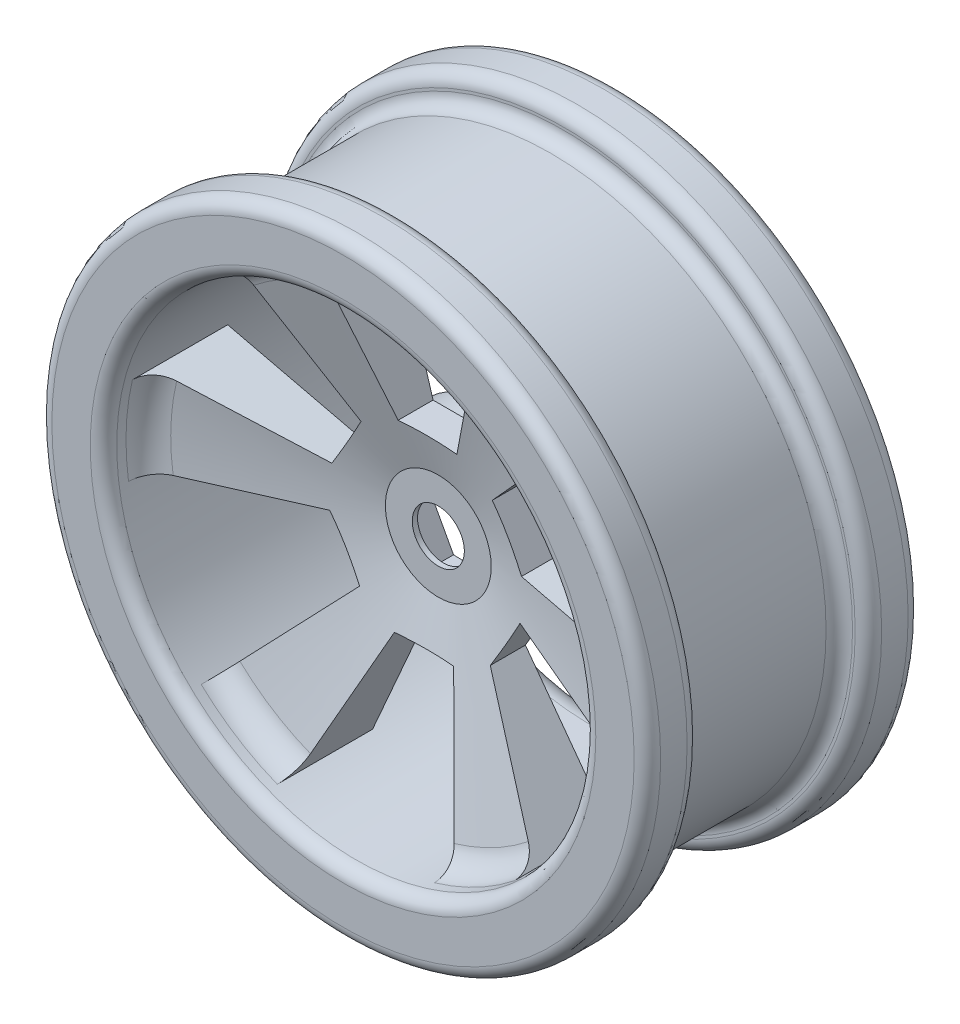
SolidWorks part; units mm, degrees
material "ABS"
ref_plane "Front Plane" through (0, 0, 0) normal (0, 0, 1) x (1, 0, 0)
ref_plane "Top Plane" through (0, 0, 0) normal (0, 1, 0) x (1, 0, 0)
ref_plane "Right Plane" through (0, 0, 0) normal (1, 0, 0) x (0, 0, -1)
sketch "Sketch1" plane through (0, 0, 0) normal (1, 0, 0) x (0, 0, -1)
  line L0 (0, 0) -> (59.5506, 0) construction
  line L1 (0, 0) -> (0, 22.987) construction
  line L2 (0, 22.987) -> (15.24, 22.987) construction
  line L3 (17.78, 25.527) -> (17.78, 27.94)
  line L4 (16.51, 29.21) -> (13.97, 29.21)
  line L5 (12.7, 27.94) -> (12.7, 27.686)
  line L6 (11.43, 26.416) -> (-2.159, 26.416)
  line L7 (-3.429, 27.686) -> (-3.429, 27.94)
  line L8 (-4.699, 29.21) -> (-7.239, 29.21)
  line L9 (-8.509, 27.94) -> (-8.509, 24.257)
  line L10 (-7.239, 22.987) -> (-6.35, 22.987)
  line L11 (0.635, 0) -> (0.635, 5.08)
  line L12 (-3.81, 0) -> (0, 0)
  line L13 (2.794, 22.987) -> (15.24, 22.987)
  line L14 (2.794, 22.987) -> (2.794, 8.4709)
  line L15 (2.794, 8.4709) -> (5.715, 8.4709)
  line L16 (5.715, 8.4709) -> (5.715, 0)
  line L17 (5.715, 0) -> (0, 0)
  line L18 (-3.9058, 21.1381) -> (0.635, 5.08)
  line L19 (5.715, 0) -> (1.143, 0) construction
  line L20 (5.715, 0) -> (5.715, 7.3033) construction
  line L21 (5.715, 7.3033) -> (1.143, 7.3033) construction
  line L22 (1.143, 0) -> (1.143, 7.3033) construction
  line L23 (5.715, 0) -> (1.143, 7.3033) construction
  line L24 (5.715, 7.3033) -> (1.143, 0) construction
  arc A0 (-6.35, 22.987) -> (-3.9058, 21.1381) centre (-6.35, 20.447) cw
  arc A1 (16.51, 29.21) -> (17.78, 27.94) centre (16.51, 27.94) cw
  arc A2 (13.97, 29.21) -> (12.7, 27.94) centre (13.97, 27.94) ccw
  arc A3 (-7.239, 29.21) -> (-8.509, 27.94) centre (-7.239, 27.94) ccw
  arc A4 (-4.699, 29.21) -> (-3.429, 27.94) centre (-4.699, 27.94) cw
  arc A5 (12.7, 27.686) -> (11.43, 26.416) centre (11.43, 27.686) cw
  arc A6 (-3.429, 27.686) -> (-2.159, 26.416) centre (-2.159, 27.686) ccw
  arc A7 (-7.239, 22.987) -> (-8.509, 24.257) centre (-7.239, 24.257) cw
  arc A8 (17.78, 25.527) -> (15.24, 22.987) centre (15.24, 25.527) cw
  point P22 (12.7, 29.21)
  point P29 (12.7, 26.416)
  point P36 (17.78, 22.987)
  point P42 (3.429, 3.6516)
  dimension "D8" = 2.54
  dimension "D9" = 1.27
  dimension "D10" = 2.54
  dimension "D11" = 45.974
  dimension "D1" = 58.42
  dimension "D2" = 2.794
  dimension "D3" = 14.986
  dimension "D4" = 5.08
  dimension "D5" = 10.16
  dimension "D6" = 26.289
  dimension "D7" = 17.78
  dimension "D12" = 16.9418
  dimension "D13" = 12.065
  dimension "D14" = 4.572
  dimension "D15" = 0.508
revolve "Body" add sketch "Sketch1" angle 360 about L0 region at (0, 24.0088, -16.7582)
sketch "Sketch2" plane through (0, 0, 0) normal (0, 0, 1) x (1, 0, 0)
  line L0 (-2.6636, 8.89) -> (2.9969, 8.89)
  line L1 (3.3042, -6.0895) -> (6.9258, -0.1832)
  line L2 (6.9258, -0.1832) -> (3.6216, 5.9063)
  line L3 (3.6216, 5.9063) -> (-3.3042, 6.0895)
  line L4 (-3.3042, 6.0895) -> (-6.9258, 0.1832)
  line L5 (-6.9258, 0.1832) -> (-3.6216, -5.9063)
  line L6 (-3.6216, -5.9063) -> (3.3042, -6.0895)
  line L7 (2.9969, 8.89) -> (8.47, 21.3696)
  line L8 (-2.6636, 8.89) -> (-6.5976, 22.0199)
  circle A0 centre (0, 0) radius 6 construction
  arc A2 (-6.5976, 22.0199) -> (8.47, 21.3696) centre (0, 0) cw
  circle A3 centre (0, 0) radius 2.5
  circle A4 centre (0, 0) radius 6.9282 construction
  dimension "D1" = 5
  dimension "D2" = 12
  dimension "D3" = 8.89
extrude "Nut" cut sketch "Sketch2" along normal blind 4.572 from surface contours L2 L3 L4 L5 L6 L1 starting at face at (8.4709, 0, -5.715)
extrude "Spokes" cut sketch "Sketch2<3>" against normal through all both and the other way through all contours L7 A2 L8 L0
sketch "Sketch2<3>" plane through (0, 0, 0) normal (0, 0, 1) x (1, 0, 0) same geometry as "Sketch2"
pattern_circular "CirPattern1" count 6 over 360 about axis through (0, 0, 0) along (0, 0, 1) of "Spokes"
extrude "Axle" cut sketch "Sketch2<4>" along normal through all both and the other way through all contours A3
sketch "Sketch2<4>" plane through (0, 0, 0) normal (0, 0, 1) x (1, 0, 0) same geometry as "Sketch2"
